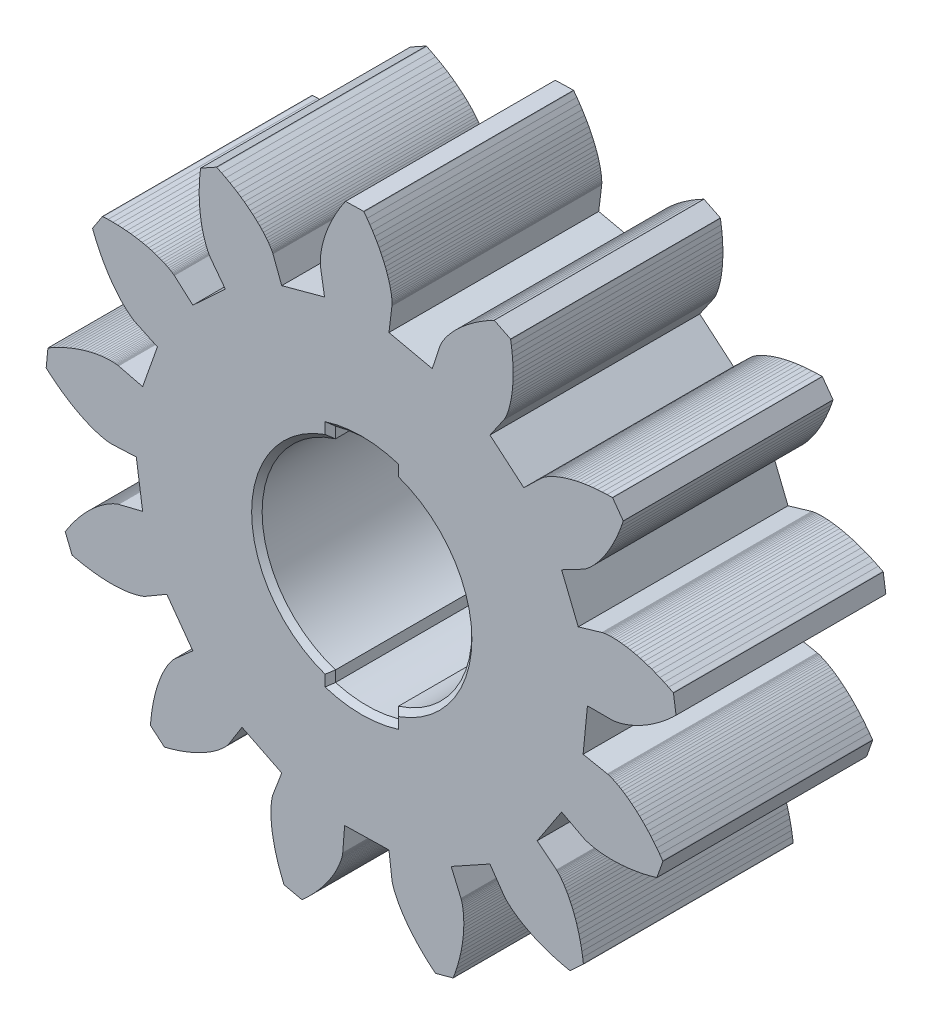
SolidWorks part; units mm, degrees
material "Stainless Steel (ferritic)"
ref_plane "Front Plane" through (0, 0, 0) normal (0, 0, 1) x (1, 0, 0)
ref_plane "Top Plane" through (0, 0, 0) normal (0, 1, 0) x (1, 0, 0)
ref_plane "Right Plane" through (0, 0, 0) normal (1, 0, 0) x (0, 0, -1)
sketch "Model" plane through (0, 0, 0) normal (0, 0, 1) x (1, 0, 0)
  line L0 (10.7591, 0) -> (11.9435, 0)
  line L1 (11.9435, 0) -> (11.9534, 0.0003)
  line L2 (11.9534, 0.0003) -> (11.9719, 0.0014)
  line L3 (11.9719, 0.0014) -> (11.9989, 0.0037)
  line L4 (11.9989, 0.0037) -> (12.0344, 0.0077)
  line L5 (12.0344, 0.0077) -> (12.0783, 0.0139)
  line L6 (12.0783, 0.0139) -> (12.1305, 0.0226)
  line L7 (12.1305, 0.0226) -> (12.191, 0.0344)
  line L8 (12.191, 0.0344) -> (12.2594, 0.0496)
  line L9 (12.2594, 0.0496) -> (12.3359, 0.0688)
  line L10 (12.3359, 0.0688) -> (12.42, 0.0923)
  line L11 (12.42, 0.0923) -> (12.5117, 0.1207)
  line L12 (12.5117, 0.1207) -> (12.6108, 0.1542)
  line L13 (12.6108, 0.1542) -> (12.717, 0.1934)
  line L14 (12.717, 0.1934) -> (12.8302, 0.2386)
  line L15 (12.8302, 0.2386) -> (12.95, 0.2902)
  line L16 (12.95, 0.2902) -> (13.0761, 0.3486)
  line L17 (13.0761, 0.3486) -> (13.2084, 0.4143)
  line L18 (13.2084, 0.4143) -> (13.3464, 0.4875)
  line L19 (13.3464, 0.4875) -> (13.49, 0.5686)
  line L20 (13.49, 0.5686) -> (13.6387, 0.6579)
  line L21 (13.6387, 0.6579) -> (13.7922, 0.7559)
  line L22 (13.7922, 0.7559) -> (13.9501, 0.8628)
  line L23 (13.9501, 0.8628) -> (14.1121, 0.9788)
  line L24 (14.1121, 0.9788) -> (14.2778, 1.1044)
  line L25 (14.2778, 1.1044) -> (14.4468, 1.2398)
  line L26 (14.4468, 1.2398) -> (14.6187, 1.3852)
  line L27 (14.6187, 1.3852) -> (14.793, 1.541)
  line L28 (14.793, 1.541) -> (14.9694, 1.7072)
  line L29 (14.9694, 1.7072) -> (14.9805, 1.718)
  line L30 (14.9805, 1.718) -> (14.9843, 1.7217)
  line L31 (14.9843, 1.7217) -> (14.8588, 2.5833)
  line L32 (14.8588, 2.5833) -> (14.8554, 2.5851)
  line L33 (14.8554, 2.5851) -> (14.8417, 2.5922)
  line L34 (14.8417, 2.5922) -> (14.6256, 2.7019)
  line L35 (14.6256, 2.7019) -> (14.4144, 2.802)
  line L36 (14.4144, 2.802) -> (14.2084, 2.8929)
  line L37 (14.2084, 2.8929) -> (14.0081, 2.975)
  line L38 (14.0081, 2.975) -> (13.8136, 3.0487)
  line L39 (13.8136, 3.0487) -> (13.6254, 3.1143)
  line L40 (13.6254, 3.1143) -> (13.4437, 3.1722)
  line L41 (13.4437, 3.1722) -> (13.2688, 3.2227)
  line L42 (13.2688, 3.2227) -> (13.1009, 3.2665)
  line L43 (13.1009, 3.2665) -> (12.9403, 3.3037)
  line L44 (12.9403, 3.3037) -> (12.7872, 3.3349)
  line L45 (12.7872, 3.3349) -> (12.6417, 3.3605)
  line L46 (12.6417, 3.3605) -> (12.5042, 3.3809)
  line L47 (12.5042, 3.3809) -> (12.3747, 3.3966)
  line L48 (12.3747, 3.3966) -> (12.2534, 3.408)
  line L49 (12.2534, 3.408) -> (12.1405, 3.4155)
  line L50 (12.1405, 3.4155) -> (12.0359, 3.4197)
  line L51 (12.0359, 3.4197) -> (11.9399, 3.4209)
  line L52 (11.9399, 3.4209) -> (11.8526, 3.4198)
  line L53 (11.8526, 3.4198) -> (11.7739, 3.4166)
  line L54 (11.7739, 3.4166) -> (11.7038, 3.4118)
  line L55 (11.7038, 3.4118) -> (11.6426, 3.406)
  line L56 (11.6426, 3.406) -> (11.59, 3.3997)
  line L57 (11.59, 3.3997) -> (11.5461, 3.3931)
  line L58 (11.5461, 3.3931) -> (11.511, 3.3869)
  line L59 (11.511, 3.3869) -> (11.4844, 3.3815)
  line L60 (11.4844, 3.3815) -> (11.4664, 3.3773)
  line L61 (11.4664, 3.3773) -> (11.4568, 3.3748)
  line L62 (11.4568, 3.3748) -> (10.3206, 3.0402)
  line L63 (10.3206, 3.0402) -> (9.5267, 5)
  line L64 (9.5267, 5) -> (10.5754, 5.5504)
  line L65 (10.5754, 5.5504) -> (10.584, 5.5553)
  line L66 (10.584, 5.5553) -> (10.5999, 5.5649)
  line L67 (10.5999, 5.5649) -> (10.6228, 5.5795)
  line L68 (10.6228, 5.5795) -> (10.6523, 5.5995)
  line L69 (10.6523, 5.5995) -> (10.6884, 5.6253)
  line L70 (10.6884, 5.6253) -> (10.7306, 5.6573)
  line L71 (10.7306, 5.6573) -> (10.7786, 5.6958)
  line L72 (10.7786, 5.6958) -> (10.8322, 5.7412)
  line L73 (10.8322, 5.7412) -> (10.8909, 5.7937)
  line L74 (10.8909, 5.7937) -> (10.9545, 5.8536)
  line L75 (10.9545, 5.8536) -> (11.0225, 5.9213)
  line L76 (11.0225, 5.9213) -> (11.0947, 5.9971)
  line L77 (11.0947, 5.9971) -> (11.1705, 6.0811)
  line L78 (11.1705, 6.0811) -> (11.2497, 6.1737)
  line L79 (11.2497, 6.1737) -> (11.3318, 6.2751)
  line L80 (11.3318, 6.2751) -> (11.4163, 6.3855)
  line L81 (11.4163, 6.3855) -> (11.5029, 6.5051)
  line L82 (11.5029, 6.5051) -> (11.5911, 6.634)
  line L83 (11.5911, 6.634) -> (11.6806, 6.7726)
  line L84 (11.6806, 6.7726) -> (11.7707, 6.9208)
  line L85 (11.7707, 6.9208) -> (11.8611, 7.0789)
  line L86 (11.8611, 7.0789) -> (11.9513, 7.2469)
  line L87 (11.9513, 7.2469) -> (12.0408, 7.425)
  line L88 (12.0408, 7.425) -> (12.1291, 7.6132)
  line L89 (12.1291, 7.6132) -> (12.2159, 7.8116)
  line L90 (12.2159, 7.8116) -> (12.3005, 8.0202)
  line L91 (12.3005, 8.0202) -> (12.3825, 8.2391)
  line L92 (12.3825, 8.2391) -> (12.4613, 8.4683)
  line L93 (12.4613, 8.4683) -> (12.4662, 8.4829)
  line L94 (12.4662, 8.4829) -> (12.4678, 8.488)
  line L95 (12.4678, 8.488) -> (11.9563, 9.1926)
  line L96 (11.9563, 9.1926) -> (11.9525, 9.1926)
  line L97 (11.9525, 9.1926) -> (11.937, 9.1926)
  line L98 (11.937, 9.1926) -> (11.6947, 9.1893)
  line L99 (11.6947, 9.1893) -> (11.4611, 9.1798)
  line L100 (11.4611, 9.1798) -> (11.2365, 9.1646)
  line L101 (11.2365, 9.1646) -> (11.0209, 9.1441)
  line L102 (11.0209, 9.1441) -> (10.8145, 9.119)
  line L103 (10.8145, 9.119) -> (10.6174, 9.0896)
  line L104 (10.6174, 9.0896) -> (10.4296, 9.0564)
  line L105 (10.4296, 9.0564) -> (10.2512, 9.0199)
  line L106 (10.2512, 9.0199) -> (10.0823, 8.9806)
  line L107 (10.0823, 8.9806) -> (9.9227, 8.9389)
  line L108 (9.9227, 8.9389) -> (9.7727, 8.8954)
  line L109 (9.7727, 8.8954) -> (9.632, 8.8505)
  line L110 (9.632, 8.8505) -> (9.5007, 8.8046)
  line L111 (9.5007, 8.8046) -> (9.3788, 8.7583)
  line L112 (9.3788, 8.7583) -> (9.2661, 8.712)
  line L113 (9.2661, 8.712) -> (9.1626, 8.6662)
  line L114 (9.1626, 8.6662) -> (9.0681, 8.6214)
  line L115 (9.0681, 8.6214) -> (8.9825, 8.5779)
  line L116 (8.9825, 8.5779) -> (8.9057, 8.5362)
  line L117 (8.9057, 8.5362) -> (8.8375, 8.4968)
  line L118 (8.8375, 8.4968) -> (8.7777, 8.4601)
  line L119 (8.7777, 8.4601) -> (8.7261, 8.4265)
  line L120 (8.7261, 8.4265) -> (8.6825, 8.3964)
  line L121 (8.6825, 8.3964) -> (8.6467, 8.3702)
  line L122 (8.6467, 8.3702) -> (8.6185, 8.3484)
  line L123 (8.6185, 8.3484) -> (8.5974, 8.3312)
  line L124 (8.5974, 8.3312) -> (8.5834, 8.3192)
  line L125 (8.5834, 8.3192) -> (8.5761, 8.3125)
  line L126 (8.5761, 8.3125) -> (7.7256, 7.4882)
  line L127 (7.7256, 7.4882) -> (6.1119, 8.8546)
  line L128 (6.1119, 8.8546) -> (6.7847, 9.8293)
  line L129 (6.7847, 9.8293) -> (6.79, 9.8376)
  line L130 (6.79, 9.8376) -> (6.7996, 9.8535)
  line L131 (6.7996, 9.8535) -> (6.8131, 9.877)
  line L132 (6.8131, 9.877) -> (6.83, 9.9085)
  line L133 (6.83, 9.9085) -> (6.8498, 9.9481)
  line L134 (6.8498, 9.9481) -> (6.8723, 9.9961)
  line L135 (6.8723, 9.9961) -> (6.897, 10.0525)
  line L136 (6.897, 10.0525) -> (6.9233, 10.1175)
  line L137 (6.9233, 10.1175) -> (6.951, 10.1913)
  line L138 (6.951, 10.1913) -> (6.9794, 10.2739)
  line L139 (6.9794, 10.2739) -> (7.0082, 10.3655)
  line L140 (7.0082, 10.3655) -> (7.0369, 10.4661)
  line L141 (7.0369, 10.4661) -> (7.065, 10.5758)
  line L142 (7.065, 10.5758) -> (7.092, 10.6945)
  line L143 (7.092, 10.6945) -> (7.1176, 10.8224)
  line L144 (7.1176, 10.8224) -> (7.1412, 10.9595)
  line L145 (7.1412, 10.9595) -> (7.1623, 11.1056)
  line L146 (7.1623, 11.1056) -> (7.1805, 11.2608)
  line L147 (7.1805, 11.2608) -> (7.1953, 11.425)
  line L148 (7.1953, 11.425) -> (7.2062, 11.5982)
  line L149 (7.2062, 11.5982) -> (7.2128, 11.7801)
  line L150 (7.2128, 11.7801) -> (7.2145, 11.9708)
  line L151 (7.2145, 11.9708) -> (7.211, 12.1701)
  line L152 (7.211, 12.1701) -> (7.2018, 12.3778)
  line L153 (7.2018, 12.3778) -> (7.1864, 12.5938)
  line L154 (7.1864, 12.5938) -> (7.1643, 12.8179)
  line L155 (7.1643, 12.8179) -> (7.1352, 13.0498)
  line L156 (7.1352, 13.0498) -> (7.0986, 13.2894)
  line L157 (7.0986, 13.2894) -> (7.096, 13.3046)
  line L158 (7.096, 13.3046) -> (7.0951, 13.3098)
  line L159 (7.0951, 13.3098) -> (6.3148, 13.696)
  line L160 (6.3148, 13.696) -> (6.3114, 13.6942)
  line L161 (6.3114, 13.6942) -> (6.2977, 13.6871)
  line L162 (6.2977, 13.6871) -> (6.0847, 13.5715)
  line L163 (6.0847, 13.5715) -> (5.8823, 13.4545)
  line L164 (5.8823, 13.4545) -> (5.6905, 13.3367)
  line L165 (5.6905, 13.3367) -> (5.5091, 13.2184)
  line L166 (5.5091, 13.2184) -> (5.338, 13.1002)
  line L167 (5.338, 13.1002) -> (5.1771, 12.9826)
  line L168 (5.1771, 12.9826) -> (5.0263, 12.8659)
  line L169 (5.0263, 12.8659) -> (4.8852, 12.7507)
  line L170 (4.8852, 12.7507) -> (4.7539, 12.6374)
  line L171 (4.7539, 12.6374) -> (4.632, 12.5264)
  line L172 (4.632, 12.5264) -> (4.5194, 12.4181)
  line L173 (4.5194, 12.4181) -> (4.4157, 12.3129)
  line L174 (4.4157, 12.3129) -> (4.3208, 12.2113)
  line L175 (4.3208, 12.2113) -> (4.2343, 12.1137)
  line L176 (4.2343, 12.1137) -> (4.156, 12.0203)
  line L177 (4.156, 12.0203) -> (4.0857, 11.9316)
  line L178 (4.0857, 11.9316) -> (4.0228, 11.848)
  line L179 (4.0228, 11.848) -> (3.9673, 11.7697)
  line L180 (3.9673, 11.7697) -> (3.9186, 11.6971)
  line L181 (3.9186, 11.6971) -> (3.8765, 11.6305)
  line L182 (3.8765, 11.6305) -> (3.8407, 11.5702)
  line L183 (3.8407, 11.5702) -> (3.8106, 11.5165)
  line L184 (3.8106, 11.5165) -> (3.786, 11.4696)
  line L185 (3.786, 11.4696) -> (3.7665, 11.4298)
  line L186 (3.7665, 11.4298) -> (3.7516, 11.3973)
  line L187 (3.7516, 11.3973) -> (3.7409, 11.3724)
  line L188 (3.7409, 11.3724) -> (3.7341, 11.3552)
  line L189 (3.7341, 11.3552) -> (3.7307, 11.3459)
  line L190 (3.7307, 11.3459) -> (3.3608, 10.2207)
  line L191 (3.3608, 10.2207) -> (1.2969, 10.6806)
  line L192 (1.2969, 10.6806) -> (1.4396, 11.8564)
  line L193 (1.4396, 11.8564) -> (1.4405, 11.8663)
  line L194 (1.4405, 11.8663) -> (1.4416, 11.8848)
  line L195 (1.4416, 11.8848) -> (1.4426, 11.9118)
  line L196 (1.4426, 11.9118) -> (1.4429, 11.9476)
  line L197 (1.4429, 11.9476) -> (1.4421, 11.9919)
  line L198 (1.4421, 11.9919) -> (1.4397, 12.0448)
  line L199 (1.4397, 12.0448) -> (1.4354, 12.1062)
  line L200 (1.4354, 12.1062) -> (1.4285, 12.176)
  line L201 (1.4285, 12.176) -> (1.4186, 12.2542)
  line L202 (1.4186, 12.2542) -> (1.4054, 12.3406)
  line L203 (1.4054, 12.3406) -> (1.3883, 12.4351)
  line L204 (1.3883, 12.4351) -> (1.367, 12.5375)
  line L205 (1.367, 12.5375) -> (1.3409, 12.6476)
  line L206 (1.3409, 12.6476) -> (1.3097, 12.7654)
  line L207 (1.3097, 12.7654) -> (1.2729, 12.8905)
  line L208 (1.2729, 12.8905) -> (1.2301, 13.0228)
  line L209 (1.2301, 13.0228) -> (1.1808, 13.162)
  line L210 (1.1808, 13.162) -> (1.1248, 13.3079)
  line L211 (1.1248, 13.3079) -> (1.0616, 13.4602)
  line L212 (1.0616, 13.4602) -> (0.9908, 13.6185)
  line L213 (0.9908, 13.6185) -> (0.9121, 13.7827)
  line L214 (0.9121, 13.7827) -> (0.825, 13.9524)
  line L215 (0.825, 13.9524) -> (0.7293, 14.1272)
  line L216 (0.7293, 14.1272) -> (0.6246, 14.3069)
  line L217 (0.6246, 14.3069) -> (0.5106, 14.4909)
  line L218 (0.5106, 14.4909) -> (0.387, 14.6791)
  line L219 (0.387, 14.6791) -> (0.2534, 14.8709)
  line L220 (0.2534, 14.8709) -> (0.1096, 15.066)
  line L221 (0.1096, 15.066) -> (0.1003, 15.0783)
  line L222 (0.1003, 15.0783) -> (0.097, 15.0825)
  line L223 (0.097, 15.0825) -> (-0.7734, 15.0619)
  line L224 (-0.7734, 15.0619) -> (-0.7756, 15.0587)
  line L225 (-0.7756, 15.0587) -> (-0.7844, 15.046)
  line L226 (-0.7844, 15.046) -> (-0.9193, 14.8446)
  line L227 (-0.9193, 14.8446) -> (-1.0441, 14.647)
  line L228 (-1.0441, 14.647) -> (-1.1592, 14.4535)
  line L229 (-1.1592, 14.4535) -> (-1.2649, 14.2645)
  line L230 (-1.2649, 14.2645) -> (-1.3614, 14.0804)
  line L231 (-1.3614, 14.0804) -> (-1.4492, 13.9014)
  line L232 (-1.4492, 13.9014) -> (-1.5286, 13.728)
  line L233 (-1.5286, 13.728) -> (-1.5999, 13.5605)
  line L234 (-1.5999, 13.5605) -> (-1.6635, 13.3991)
  line L235 (-1.6635, 13.3991) -> (-1.7198, 13.2441)
  line L236 (-1.7198, 13.2441) -> (-1.7693, 13.0959)
  line L237 (-1.7693, 13.0959) -> (-1.8122, 12.9546)
  line L238 (-1.8122, 12.9546) -> (-1.849, 12.8206)
  line L239 (-1.849, 12.8206) -> (-1.8802, 12.6939)
  line L240 (-1.8802, 12.6939) -> (-1.9061, 12.5749)
  line L241 (-1.9061, 12.5749) -> (-1.9272, 12.4636)
  line L242 (-1.9272, 12.4636) -> (-1.944, 12.3604)
  line L243 (-1.944, 12.3604) -> (-1.9568, 12.2652)
  line L244 (-1.9568, 12.2652) -> (-1.9661, 12.1784)
  line L245 (-1.9661, 12.1784) -> (-1.9725, 12.0998)
  line L246 (-1.9725, 12.0998) -> (-1.9762, 12.0298)
  line L247 (-1.9762, 12.0298) -> (-1.9779, 11.9682)
  line L248 (-1.9779, 11.9682) -> (-1.9779, 11.9153)
  line L249 (-1.9779, 11.9153) -> (-1.9767, 11.871)
  line L250 (-1.9767, 11.871) -> (-1.9747, 11.8353)
  line L251 (-1.9747, 11.8353) -> (-1.9726, 11.8082)
  line L252 (-1.9726, 11.8082) -> (-1.9706, 11.7898)
  line L253 (-1.9706, 11.7898) -> (-1.9693, 11.78)
  line L254 (-1.9693, 11.78) -> (-1.774, 10.6118)
  line L255 (-1.774, 10.6118) -> (-3.8152, 10.0599)
  line L256 (-3.8152, 10.0599) -> (-4.2352, 11.1674)
  line L257 (-4.2352, 11.1674) -> (-4.2391, 11.1765)
  line L258 (-4.2391, 11.1765) -> (-4.2466, 11.1934)
  line L259 (-4.2466, 11.1934) -> (-4.2584, 11.2178)
  line L260 (-4.2584, 11.2178) -> (-4.2747, 11.2496)
  line L261 (-4.2747, 11.2496) -> (-4.296, 11.2885)
  line L262 (-4.296, 11.2885) -> (-4.3227, 11.3342)
  line L263 (-4.3227, 11.3342) -> (-4.3551, 11.3866)
  line L264 (-4.3551, 11.3866) -> (-4.3936, 11.4452)
  line L265 (-4.3936, 11.4452) -> (-4.4387, 11.5098)
  line L266 (-4.4387, 11.5098) -> (-4.4905, 11.5802)
  line L267 (-4.4905, 11.5802) -> (-4.5495, 11.6559)
  line L268 (-4.5495, 11.6559) -> (-4.616, 11.7366)
  line L269 (-4.616, 11.7366) -> (-4.6903, 11.8221)
  line L270 (-4.6903, 11.8221) -> (-4.7727, 11.9118)
  line L271 (-4.7727, 11.9118) -> (-4.8635, 12.0055)
  line L272 (-4.8635, 12.0055) -> (-4.9628, 12.1027)
  line L273 (-4.9628, 12.1027) -> (-5.0711, 12.2031)
  line L274 (-5.0711, 12.2031) -> (-5.1885, 12.3063)
  line L275 (-5.1885, 12.3063) -> (-5.3152, 12.4117)
  line L276 (-5.3152, 12.4117) -> (-5.4515, 12.5191)
  line L277 (-5.4515, 12.5191) -> (-5.5976, 12.6279)
  line L278 (-5.5976, 12.6279) -> (-5.7535, 12.7377)
  line L279 (-5.7535, 12.7377) -> (-5.9195, 12.848)
  line L280 (-5.9195, 12.848) -> (-6.0957, 12.9584)
  line L281 (-6.0957, 12.9584) -> (-6.2822, 13.0684)
  line L282 (-6.2822, 13.0684) -> (-6.4791, 13.1775)
  line L283 (-6.4791, 13.1775) -> (-6.6865, 13.2853)
  line L284 (-6.6865, 13.2853) -> (-6.9045, 13.3912)
  line L285 (-6.9045, 13.3912) -> (-6.9185, 13.3978)
  line L286 (-6.9185, 13.3978) -> (-6.9233, 13.4)
  line L287 (-6.9233, 13.4) -> (-7.6844, 12.9772)
  line L288 (-7.6844, 12.9772) -> (-7.6849, 12.9734)
  line L289 (-7.6849, 12.9734) -> (-7.6867, 12.958)
  line L290 (-7.6867, 12.958) -> (-7.7126, 12.7171)
  line L291 (-7.7126, 12.7171) -> (-7.7313, 12.4841)
  line L292 (-7.7313, 12.4841) -> (-7.7433, 12.2592)
  line L293 (-7.7433, 12.2592) -> (-7.749, 12.0428)
  line L294 (-7.749, 12.0428) -> (-7.749, 11.8349)
  line L295 (-7.749, 11.8349) -> (-7.7435, 11.6356)
  line L296 (-7.7435, 11.6356) -> (-7.7332, 11.4452)
  line L297 (-7.7332, 11.4452) -> (-7.7185, 11.2637)
  line L298 (-7.7185, 11.2637) -> (-7.6998, 11.0912)
  line L299 (-7.6998, 11.0912) -> (-7.6777, 10.9279)
  line L300 (-7.6777, 10.9279) -> (-7.6526, 10.7736)
  line L301 (-7.6526, 10.7736) -> (-7.6249, 10.6286)
  line L302 (-7.6249, 10.6286) -> (-7.5952, 10.4927)
  line L303 (-7.5952, 10.4927) -> (-7.564, 10.3661)
  line L304 (-7.564, 10.3661) -> (-7.5316, 10.2487)
  line L305 (-7.5316, 10.2487) -> (-7.4986, 10.1404)
  line L306 (-7.4986, 10.1404) -> (-7.4655, 10.0412)
  line L307 (-7.4655, 10.0412) -> (-7.4326, 9.951)
  line L308 (-7.4326, 9.951) -> (-7.4005, 9.8697)
  line L309 (-7.4005, 9.8697) -> (-7.3696, 9.7972)
  line L310 (-7.3696, 9.7972) -> (-7.3404, 9.7334)
  line L311 (-7.3404, 9.7334) -> (-7.3132, 9.6782)
  line L312 (-7.3132, 9.6782) -> (-7.2886, 9.6313)
  line L313 (-7.2886, 9.6313) -> (-7.267, 9.5926)
  line L314 (-7.267, 9.5926) -> (-7.2487, 9.5619)
  line L315 (-7.2487, 9.5619) -> (-7.2342, 9.539)
  line L316 (-7.2342, 9.539) -> (-7.2239, 9.5236)
  line L317 (-7.2239, 9.5236) -> (-7.2182, 9.5155)
  line L318 (-7.2182, 9.5155) -> (-6.5024, 8.5719)
  line L319 (-6.5024, 8.5719) -> (-8.0533, 7.1346)
  line L320 (-8.0533, 7.1346) -> (-8.9398, 7.92)
  line L321 (-8.9398, 7.92) -> (-8.9475, 7.9263)
  line L322 (-8.9475, 7.9263) -> (-8.962, 7.9377)
  line L323 (-8.962, 7.9377) -> (-8.9838, 7.9539)
  line L324 (-8.9838, 7.9539) -> (-9.013, 7.9745)
  line L325 (-9.013, 7.9745) -> (-9.0499, 7.999)
  line L326 (-9.0499, 7.999) -> (-9.0948, 8.0271)
  line L327 (-9.0948, 8.0271) -> (-9.1478, 8.0584)
  line L328 (-9.1478, 8.0584) -> (-9.2092, 8.0924)
  line L329 (-9.2092, 8.0924) -> (-9.2791, 8.1287)
  line L330 (-9.2791, 8.1287) -> (-9.3577, 8.1669)
  line L331 (-9.3577, 8.1669) -> (-9.4452, 8.2065)
  line L332 (-9.4452, 8.2065) -> (-9.5416, 8.2471)
  line L333 (-9.5416, 8.2471) -> (-9.6471, 8.2882)
  line L334 (-9.6471, 8.2882) -> (-9.7617, 8.3294)
  line L335 (-9.7617, 8.3294) -> (-9.8856, 8.3702)
  line L336 (-9.8856, 8.3702) -> (-10.0188, 8.4101)
  line L337 (-10.0188, 8.4101) -> (-10.1613, 8.4487)
  line L338 (-10.1613, 8.4487) -> (-10.3132, 8.4855)
  line L339 (-10.3132, 8.4855) -> (-10.4744, 8.5199)
  line L340 (-10.4744, 8.5199) -> (-10.645, 8.5516)
  line L341 (-10.645, 8.5516) -> (-10.8248, 8.5801)
  line L342 (-10.8248, 8.5801) -> (-11.0139, 8.6049)
  line L343 (-11.0139, 8.6049) -> (-11.2122, 8.6254)
  line L344 (-11.2122, 8.6254) -> (-11.4195, 8.6413)
  line L345 (-11.4195, 8.6413) -> (-11.6358, 8.652)
  line L346 (-11.6358, 8.652) -> (-11.8608, 8.6571)
  line L347 (-11.8608, 8.6571) -> (-12.0946, 8.6562)
  line L348 (-12.0946, 8.6562) -> (-12.3368, 8.6487)
  line L349 (-12.3368, 8.6487) -> (-12.3522, 8.648)
  line L350 (-12.3522, 8.648) -> (-12.3575, 8.6477)
  line L351 (-12.3575, 8.6477) -> (-12.835, 7.9196)
  line L352 (-12.835, 7.9196) -> (-12.8336, 7.916)
  line L353 (-12.8336, 7.916) -> (-12.8282, 7.9016)
  line L354 (-12.8282, 7.9016) -> (-12.7391, 7.6762)
  line L355 (-12.7391, 7.6762) -> (-12.6474, 7.4612)
  line L356 (-12.6474, 7.4612) -> (-12.5535, 7.2565)
  line L357 (-12.5535, 7.2565) -> (-12.458, 7.0622)
  line L358 (-12.458, 7.0622) -> (-12.3613, 6.8781)
  line L359 (-12.3613, 6.8781) -> (-12.2639, 6.7042)
  line L360 (-12.2639, 6.7042) -> (-12.1663, 6.5404)
  line L361 (-12.1663, 6.5404) -> (-12.0689, 6.3866)
  line L362 (-12.0689, 6.3866) -> (-11.9722, 6.2425)
  line L363 (-11.9722, 6.2425) -> (-11.8767, 6.1081)
  line L364 (-11.8767, 6.1081) -> (-11.7828, 5.9833)
  line L365 (-11.7828, 5.9833) -> (-11.6909, 5.8677)
  line L366 (-11.6909, 5.8677) -> (-11.6015, 5.7612)
  line L367 (-11.6015, 5.7612) -> (-11.5149, 5.6636)
  line L368 (-11.5149, 5.6636) -> (-11.4317, 5.5746)
  line L369 (-11.4317, 5.5746) -> (-11.3522, 5.4941)
  line L370 (-11.3522, 5.4941) -> (-11.2767, 5.4216)
  line L371 (-11.2767, 5.4216) -> (-11.2057, 5.357)
  line L372 (-11.2057, 5.357) -> (-11.1395, 5.3)
  line L373 (-11.1395, 5.3) -> (-11.0785, 5.2502)
  line L374 (-11.0785, 5.2502) -> (-11.0229, 5.2073)
  line L375 (-11.0229, 5.2073) -> (-10.9732, 5.171)
  line L376 (-10.9732, 5.171) -> (-10.9296, 5.1409)
  line L377 (-10.9296, 5.1409) -> (-10.8925, 5.1167)
  line L378 (-10.8925, 5.1167) -> (-10.862, 5.098)
  line L379 (-10.862, 5.098) -> (-10.8385, 5.0845)
  line L380 (-10.8385, 5.0845) -> (-10.8223, 5.0756)
  line L381 (-10.8223, 5.0756) -> (-10.8134, 5.0711)
  line L382 (-10.8134, 5.0711) -> (-9.7411, 4.5682)
  line L383 (-9.7411, 4.5682) -> (-10.4465, 2.5748)
  line L384 (-10.4465, 2.5748) -> (-11.5964, 2.8582)
  line L385 (-11.5964, 2.8582) -> (-11.6061, 2.8603)
  line L386 (-11.6061, 2.8603) -> (-11.6243, 2.8637)
  line L387 (-11.6243, 2.8637) -> (-11.6511, 2.8679)
  line L388 (-11.6511, 2.8679) -> (-11.6866, 2.8725)
  line L389 (-11.6866, 2.8725) -> (-11.7307, 2.8771)
  line L390 (-11.7307, 2.8771) -> (-11.7834, 2.8811)
  line L391 (-11.7834, 2.8811) -> (-11.8449, 2.8841)
  line L392 (-11.8449, 2.8841) -> (-11.9151, 2.8857)
  line L393 (-11.9151, 2.8857) -> (-11.9939, 2.8854)
  line L394 (-11.9939, 2.8854) -> (-12.0812, 2.8827)
  line L395 (-12.0812, 2.8827) -> (-12.177, 2.8771)
  line L396 (-12.177, 2.8771) -> (-12.2813, 2.8682)
  line L397 (-12.2813, 2.8682) -> (-12.3938, 2.8556)
  line L398 (-12.3938, 2.8556) -> (-12.5144, 2.8388)
  line L399 (-12.5144, 2.8388) -> (-12.6431, 2.8174)
  line L400 (-12.6431, 2.8174) -> (-12.7796, 2.7908)
  line L401 (-12.7796, 2.7908) -> (-12.9237, 2.7587)
  line L402 (-12.9237, 2.7587) -> (-13.0753, 2.7207)
  line L403 (-13.0753, 2.7207) -> (-13.2341, 2.6763)
  line L404 (-13.2341, 2.6763) -> (-13.3998, 2.6251)
  line L405 (-13.3998, 2.6251) -> (-13.5723, 2.5668)
  line L406 (-13.5723, 2.5668) -> (-13.7512, 2.5008)
  line L407 (-13.7512, 2.5008) -> (-13.9363, 2.4269)
  line L408 (-13.9363, 2.4269) -> (-14.1273, 2.3446)
  line L409 (-14.1273, 2.3446) -> (-14.3237, 2.2536)
  line L410 (-14.3237, 2.2536) -> (-14.5254, 2.1535)
  line L411 (-14.5254, 2.1535) -> (-14.7319, 2.044)
  line L412 (-14.7319, 2.044) -> (-14.943, 1.9248)
  line L413 (-14.943, 1.9248) -> (-14.9563, 1.917)
  line L414 (-14.9563, 1.917) -> (-14.9609, 1.9143)
  line L415 (-14.9609, 1.9143) -> (-15.0453, 1.0477)
  line L416 (-15.0453, 1.0477) -> (-15.0424, 1.0452)
  line L417 (-15.0424, 1.0452) -> (-15.0308, 1.0349)
  line L418 (-15.0308, 1.0349) -> (-14.8472, 0.8768)
  line L419 (-14.8472, 0.8768) -> (-14.6661, 0.729)
  line L420 (-14.6661, 0.729) -> (-14.4879, 0.5914)
  line L421 (-14.4879, 0.5914) -> (-14.313, 0.4637)
  line L422 (-14.313, 0.4637) -> (-14.1418, 0.3457)
  line L423 (-14.1418, 0.3457) -> (-13.9748, 0.237)
  line L424 (-13.9748, 0.237) -> (-13.8122, 0.1373)
  line L425 (-13.8122, 0.1373) -> (-13.6545, 0.0463)
  line L426 (-13.6545, 0.0463) -> (-13.5019, -0.0363)
  line L427 (-13.5019, -0.0363) -> (-13.3549, -0.1109)
  line L428 (-13.3549, -0.1109) -> (-13.2137, -0.1778)
  line L429 (-13.2137, -0.1778) -> (-13.0786, -0.2375)
  line L430 (-13.0786, -0.2375) -> (-12.95, -0.2902)
  line L431 (-12.95, -0.2902) -> (-12.828, -0.3364)
  line L432 (-12.828, -0.3364) -> (-12.7129, -0.3765)
  line L433 (-12.7129, -0.3765) -> (-12.6051, -0.4109)
  line L434 (-12.6051, -0.4109) -> (-12.5046, -0.4399)
  line L435 (-12.5046, -0.4399) -> (-12.4117, -0.4641)
  line L436 (-12.4117, -0.4641) -> (-12.3265, -0.4839)
  line L437 (-12.3265, -0.4839) -> (-12.2494, -0.4996)
  line L438 (-12.2494, -0.4996) -> (-12.1803, -0.5118)
  line L439 (-12.1803, -0.5118) -> (-12.1194, -0.5208)
  line L440 (-12.1194, -0.5208) -> (-12.0668, -0.5272)
  line L441 (-12.0668, -0.5272) -> (-12.0227, -0.5314)
  line L442 (-12.0227, -0.5314) -> (-11.987, -0.5338)
  line L443 (-11.987, -0.5338) -> (-11.9599, -0.5349)
  line L444 (-11.9599, -0.5349) -> (-11.9414, -0.5351)
  line L445 (-11.9414, -0.5351) -> (-11.9315, -0.535)
  line L446 (-11.9315, -0.535) -> (-10.7483, -0.482)
  line L447 (-10.7483, -0.482) -> (-10.4465, -2.5748)
  line L448 (-10.4465, -2.5748) -> (-11.5964, -2.8583)
  line L449 (-11.5964, -2.8583) -> (-11.606, -2.861)
  line L450 (-11.606, -2.861) -> (-11.6236, -2.8664)
  line L451 (-11.6236, -2.8664) -> (-11.6493, -2.8752)
  line L452 (-11.6493, -2.8752) -> (-11.6828, -2.8875)
  line L453 (-11.6828, -2.8875) -> (-11.724, -2.904)
  line L454 (-11.724, -2.904) -> (-11.7726, -2.925)
  line L455 (-11.7726, -2.925) -> (-11.8285, -2.9508)
  line L456 (-11.8285, -2.9508) -> (-11.8913, -2.982)
  line L457 (-11.8913, -2.982) -> (-11.9609, -3.019)
  line L458 (-11.9609, -3.019) -> (-12.037, -3.0619)
  line L459 (-12.037, -3.0619) -> (-12.1193, -3.1114)
  line L460 (-12.1193, -3.1114) -> (-12.2075, -3.1677)
  line L461 (-12.2075, -3.1677) -> (-12.3012, -3.2311)
  line L462 (-12.3012, -3.2311) -> (-12.4003, -3.3021)
  line L463 (-12.4003, -3.3021) -> (-12.5042, -3.3809)
  line L464 (-12.5042, -3.3809) -> (-12.6127, -3.4678)
  line L465 (-12.6127, -3.4678) -> (-12.7254, -3.5632)
  line L466 (-12.7254, -3.5632) -> (-12.842, -3.6673)
  line L467 (-12.842, -3.6673) -> (-12.9619, -3.7804)
  line L468 (-12.9619, -3.7804) -> (-13.0849, -3.9028)
  line L469 (-13.0849, -3.9028) -> (-13.2105, -4.0346)
  line L470 (-13.2105, -4.0346) -> (-13.3383, -4.1762)
  line L471 (-13.3383, -4.1762) -> (-13.4678, -4.3277)
  line L472 (-13.4678, -4.3277) -> (-13.5986, -4.4893)
  line L473 (-13.5986, -4.4893) -> (-13.7303, -4.6611)
  line L474 (-13.7303, -4.6611) -> (-13.8624, -4.8435)
  line L475 (-13.8624, -4.8435) -> (-13.9944, -5.0364)
  line L476 (-13.9944, -5.0364) -> (-14.1258, -5.24)
  line L477 (-14.1258, -5.24) -> (-14.134, -5.2531)
  line L478 (-14.134, -5.2531) -> (-14.1368, -5.2576)
  line L479 (-14.1368, -5.2576) -> (-13.8088, -6.0642)
  line L480 (-13.8088, -6.0642) -> (-13.8051, -6.0651)
  line L481 (-13.8051, -6.0651) -> (-13.7901, -6.0688)
  line L482 (-13.7901, -6.0688) -> (-13.554, -6.1235)
  line L483 (-13.554, -6.1235) -> (-13.325, -6.1702)
  line L484 (-13.325, -6.1702) -> (-13.1032, -6.2092)
  line L485 (-13.1032, -6.2092) -> (-12.889, -6.241)
  line L486 (-12.889, -6.241) -> (-12.6826, -6.2659)
  line L487 (-12.6826, -6.2659) -> (-12.4842, -6.2846)
  line L488 (-12.4842, -6.2846) -> (-12.2939, -6.2973)
  line L489 (-12.2939, -6.2973) -> (-12.1119, -6.3045)
  line L490 (-12.1119, -6.3045) -> (-11.9385, -6.3068)
  line L491 (-11.9385, -6.3068) -> (-11.7736, -6.3045)
  line L492 (-11.7736, -6.3045) -> (-11.6175, -6.2982)
  line L493 (-11.6175, -6.2982) -> (-11.4702, -6.2882)
  line L494 (-11.4702, -6.2882) -> (-11.3318, -6.2751)
  line L495 (-11.3318, -6.2751) -> (-11.2023, -6.2593)
  line L496 (-11.2023, -6.2593) -> (-11.0818, -6.2414)
  line L497 (-11.0818, -6.2414) -> (-10.9703, -6.2217)
  line L498 (-10.9703, -6.2217) -> (-10.8678, -6.2007)
  line L499 (-10.8678, -6.2007) -> (-10.7743, -6.179)
  line L500 (-10.7743, -6.179) -> (-10.6897, -6.1569)
  line L501 (-10.6897, -6.1569) -> (-10.6141, -6.1349)
  line L502 (-10.6141, -6.1349) -> (-10.5472, -6.1136)
  line L503 (-10.5472, -6.1136) -> (-10.4891, -6.0933)
  line L504 (-10.4891, -6.0933) -> (-10.4396, -6.0745)
  line L505 (-10.4396, -6.0745) -> (-10.3986, -6.0577)
  line L506 (-10.3986, -6.0577) -> (-10.3659, -6.0433)
  line L507 (-10.3659, -6.0433) -> (-10.3414, -6.0316)
  line L508 (-10.3414, -6.0316) -> (-10.3249, -6.0233)
  line L509 (-10.3249, -6.0233) -> (-10.3162, -6.0186)
  line L510 (-10.3162, -6.0186) -> (-9.2932, -5.4217)
  line L511 (-9.2932, -5.4217) -> (-8.0533, -7.1346)
  line L512 (-8.0533, -7.1346) -> (-8.9398, -7.92)
  line L513 (-8.9398, -7.92) -> (-8.947, -7.9268)
  line L514 (-8.947, -7.9268) -> (-8.9601, -7.9399)
  line L515 (-8.9601, -7.9399) -> (-8.9788, -7.9595)
  line L516 (-8.9788, -7.9595) -> (-9.0027, -7.9861)
  line L517 (-9.0027, -7.9861) -> (-9.0316, -8.0198)
  line L518 (-9.0316, -8.0198) -> (-9.0649, -8.0609)
  line L519 (-9.0649, -8.0609) -> (-9.1023, -8.1098)
  line L520 (-9.1023, -8.1098) -> (-9.1434, -8.1667)
  line L521 (-9.1434, -8.1667) -> (-9.1879, -8.2317)
  line L522 (-9.1879, -8.2317) -> (-9.2353, -8.3051)
  line L523 (-9.2353, -8.3051) -> (-9.2852, -8.3871)
  line L524 (-9.2852, -8.3871) -> (-9.3371, -8.4779)
  line L525 (-9.3371, -8.4779) -> (-9.3906, -8.5777)
  line L526 (-9.3906, -8.5777) -> (-9.4453, -8.6865)
  line L527 (-9.4453, -8.6865) -> (-9.5007, -8.8046)
  line L528 (-9.5007, -8.8046) -> (-9.5564, -8.932)
  line L529 (-9.5564, -8.932) -> (-9.6119, -9.0689)
  line L530 (-9.6119, -9.0689) -> (-9.6667, -9.2152)
  line L531 (-9.6667, -9.2152) -> (-9.7204, -9.3711)
  line L532 (-9.7204, -9.3711) -> (-9.7724, -9.5366)
  line L533 (-9.7724, -9.5366) -> (-9.8223, -9.7117)
  line L534 (-9.8223, -9.7117) -> (-9.8697, -9.8964)
  line L535 (-9.8697, -9.8964) -> (-9.914, -10.0908)
  line L536 (-9.914, -10.0908) -> (-9.9547, -10.2946)
  line L537 (-9.9547, -10.2946) -> (-9.9915, -10.508)
  line L538 (-9.9915, -10.508) -> (-10.0237, -10.7309)
  line L539 (-10.0237, -10.7309) -> (-10.0509, -10.963)
  line L540 (-10.0509, -10.963) -> (-10.0726, -11.2044)
  line L541 (-10.0726, -11.2044) -> (-10.0738, -11.2198)
  line L542 (-10.0738, -11.2198) -> (-10.0742, -11.2251)
  line L543 (-10.0742, -11.2251) -> (-9.409, -11.7868)
  line L544 (-9.409, -11.7868) -> (-9.4052, -11.7859)
  line L545 (-9.4052, -11.7859) -> (-9.3902, -11.7822)
  line L546 (-9.3902, -11.7822) -> (-9.1557, -11.721)
  line L547 (-9.1557, -11.721) -> (-8.9312, -11.6558)
  line L548 (-8.9312, -11.6558) -> (-8.7168, -11.5873)
  line L549 (-8.7168, -11.5873) -> (-8.5124, -11.5159)
  line L550 (-8.5124, -11.5159) -> (-8.318, -11.4421)
  line L551 (-8.318, -11.4421) -> (-8.1336, -11.3664)
  line L552 (-8.1336, -11.3664) -> (-7.9592, -11.2892)
  line L553 (-7.9592, -11.2892) -> (-7.7947, -11.2111)
  line L554 (-7.7947, -11.2111) -> (-7.6401, -11.1325)
  line L555 (-7.6401, -11.1325) -> (-7.4952, -11.0538)
  line L556 (-7.4952, -11.0538) -> (-7.3599, -10.9757)
  line L557 (-7.3599, -10.9757) -> (-7.2341, -10.8984)
  line L558 (-7.2341, -10.8984) -> (-7.1176, -10.8224)
  line L559 (-7.1176, -10.8224) -> (-7.0103, -10.7483)
  line L560 (-7.0103, -10.7483) -> (-6.9119, -10.6764)
  line L561 (-6.9119, -10.6764) -> (-6.8224, -10.6072)
  line L562 (-6.8224, -10.6072) -> (-6.7414, -10.541)
  line L563 (-6.7414, -10.541) -> (-6.6687, -10.4783)
  line L564 (-6.6687, -10.4783) -> (-6.6041, -10.4194)
  line L565 (-6.6041, -10.4194) -> (-6.5473, -10.3648)
  line L566 (-6.5473, -10.3648) -> (-6.498, -10.3149)
  line L567 (-6.498, -10.3149) -> (-6.456, -10.2699)
  line L568 (-6.456, -10.2699) -> (-6.4209, -10.2303)
  line L569 (-6.4209, -10.2303) -> (-6.3923, -10.1963)
  line L570 (-6.3923, -10.1963) -> (-6.3701, -10.1683)
  line L571 (-6.3701, -10.1683) -> (-6.3538, -10.1466)
  line L572 (-6.3538, -10.1466) -> (-6.3431, -10.1316)
  line L573 (-6.3431, -10.1316) -> (-6.3376, -10.1233)
  line L574 (-6.3376, -10.1233) -> (-5.7091, -9.1195)
  line L575 (-5.7091, -9.1195) -> (-3.8152, -10.0599)
  line L576 (-3.8152, -10.0599) -> (-4.2352, -11.1674)
  line L577 (-4.2352, -11.1674) -> (-4.2384, -11.1767)
  line L578 (-4.2384, -11.1767) -> (-4.2439, -11.1944)
  line L579 (-4.2439, -11.1944) -> (-4.2514, -11.2205)
  line L580 (-4.2514, -11.2205) -> (-4.2602, -11.2551)
  line L581 (-4.2602, -11.2551) -> (-4.2701, -11.2983)
  line L582 (-4.2701, -11.2983) -> (-4.2804, -11.3503)
  line L583 (-4.2804, -11.3503) -> (-4.2909, -11.4109)
  line L584 (-4.2909, -11.4109) -> (-4.3009, -11.4804)
  line L585 (-4.3009, -11.4804) -> (-4.31, -11.5586)
  line L586 (-4.31, -11.5586) -> (-4.3179, -11.6456)
  line L587 (-4.3179, -11.6456) -> (-4.3239, -11.7415)
  line L588 (-4.3239, -11.7415) -> (-4.3277, -11.846)
  line L589 (-4.3277, -11.846) -> (-4.3287, -11.9592)
  line L590 (-4.3287, -11.9592) -> (-4.3266, -12.081)
  line L591 (-4.3266, -12.081) -> (-4.3208, -12.2113)
  line L592 (-4.3208, -12.2113) -> (-4.3109, -12.35)
  line L593 (-4.3109, -12.35) -> (-4.2964, -12.497)
  line L594 (-4.2964, -12.497) -> (-4.2769, -12.652)
  line L595 (-4.2769, -12.652) -> (-4.252, -12.815)
  line L596 (-4.252, -12.815) -> (-4.2212, -12.9857)
  line L597 (-4.2212, -12.9857) -> (-4.184, -13.164)
  line L598 (-4.184, -13.164) -> (-4.1401, -13.3495)
  line L599 (-4.1401, -13.3495) -> (-4.089, -13.5422)
  line L600 (-4.089, -13.5422) -> (-4.0303, -13.7416)
  line L601 (-4.0303, -13.7416) -> (-3.9637, -13.9477)
  line L602 (-3.9637, -13.9477) -> (-3.8886, -14.1599)
  line L603 (-3.8886, -14.1599) -> (-3.8049, -14.3782)
  line L604 (-3.8049, -14.3782) -> (-3.7119, -14.602)
  line L605 (-3.7119, -14.602) -> (-3.7058, -14.6162)
  line L606 (-3.7058, -14.6162) -> (-3.7037, -14.621)
  line L607 (-3.7037, -14.621) -> (-2.8536, -14.8093)
  line L608 (-2.8536, -14.8093) -> (-2.8507, -14.8067)
  line L609 (-2.8507, -14.8067) -> (-2.8392, -14.7965)
  line L610 (-2.8392, -14.7965) -> (-2.66, -14.6333)
  line L611 (-2.66, -14.6333) -> (-2.4915, -14.4713)
  line L612 (-2.4915, -14.4713) -> (-2.3334, -14.311)
  line L613 (-2.3334, -14.311) -> (-2.1856, -14.1527)
  line L614 (-2.1856, -14.1527) -> (-2.0478, -13.997)
  line L615 (-2.0478, -13.997) -> (-1.9197, -13.8443)
  line L616 (-1.9197, -13.8443) -> (-1.8012, -13.6949)
  line L617 (-1.8012, -13.6949) -> (-1.6919, -13.5493)
  line L618 (-1.6919, -13.5493) -> (-1.5915, -13.4078)
  line L619 (-1.5915, -13.4078) -> (-1.4997, -13.2709)
  line L620 (-1.4997, -13.2709) -> (-1.4162, -13.1388)
  line L621 (-1.4162, -13.1388) -> (-1.3407, -13.0119)
  line L622 (-1.3407, -13.0119) -> (-1.2729, -12.8905)
  line L623 (-1.2729, -12.8905) -> (-1.2123, -12.775)
  line L624 (-1.2123, -12.775) -> (-1.1586, -12.6656)
  line L625 (-1.1586, -12.6656) -> (-1.1115, -12.5627)
  line L626 (-1.1115, -12.5627) -> (-1.0705, -12.4664)
  line L627 (-1.0705, -12.4664) -> (-1.0353, -12.3771)
  line L628 (-1.0353, -12.3771) -> (-1.0055, -12.295)
  line L629 (-1.0055, -12.295) -> (-0.9805, -12.2203)
  line L630 (-0.9805, -12.2203) -> (-0.9601, -12.1531)
  line L631 (-0.9601, -12.1531) -> (-0.9438, -12.0938)
  line L632 (-0.9438, -12.0938) -> (-0.9311, -12.0424)
  line L633 (-0.9311, -12.0424) -> (-0.9217, -11.999)
  line L634 (-0.9217, -11.999) -> (-0.915, -11.9639)
  line L635 (-0.915, -11.9639) -> (-0.9107, -11.9372)
  line L636 (-0.9107, -11.9372) -> (-0.9082, -11.9188)
  line L637 (-0.9082, -11.9188) -> (-0.9071, -11.909)
  line L638 (-0.9071, -11.909) -> (-0.8171, -10.728)
  line L639 (-0.8171, -10.728) -> (1.2969, -10.6806)
  line L640 (1.2969, -10.6806) -> (1.4396, -11.8564)
  line L641 (1.4396, -11.8564) -> (1.4412, -11.8662)
  line L642 (1.4412, -11.8662) -> (1.4445, -11.8844)
  line L643 (1.4445, -11.8844) -> (1.45, -11.911)
  line L644 (1.45, -11.911) -> (1.4583, -11.9457)
  line L645 (1.4583, -11.9457) -> (1.4696, -11.9886)
  line L646 (1.4696, -11.9886) -> (1.4846, -12.0394)
  line L647 (1.4846, -12.0394) -> (1.5036, -12.0979)
  line L648 (1.5036, -12.0979) -> (1.527, -12.1641)
  line L649 (1.527, -12.1641) -> (1.5552, -12.2376)
  line L650 (1.5552, -12.2376) -> (1.5887, -12.3183)
  line L651 (1.5887, -12.3183) -> (1.6279, -12.406)
  line L652 (1.6279, -12.406) -> (1.6731, -12.5003)
  line L653 (1.6731, -12.5003) -> (1.7248, -12.601)
  line L654 (1.7248, -12.601) -> (1.7833, -12.7079)
  line L655 (1.7833, -12.7079) -> (1.849, -12.8206)
  line L656 (1.849, -12.8206) -> (1.9222, -12.9387)
  line L657 (1.9222, -12.9387) -> (2.0033, -13.0621)
  line L658 (2.0033, -13.0621) -> (2.0926, -13.1904)
  line L659 (2.0926, -13.1904) -> (2.1905, -13.3231)
  line L660 (2.1905, -13.3231) -> (2.2971, -13.4599)
  line L661 (2.2971, -13.4599) -> (2.4129, -13.6005)
  line L662 (2.4129, -13.6005) -> (2.538, -13.7444)
  line L663 (2.538, -13.7444) -> (2.6727, -13.8913)
  line L664 (2.6727, -13.8913) -> (2.8174, -14.0406)
  line L665 (2.8174, -14.0406) -> (2.9721, -14.1921)
  line L666 (2.9721, -14.1921) -> (3.1372, -14.3451)
  line L667 (3.1372, -14.3451) -> (3.3128, -14.4994)
  line L668 (3.3128, -14.4994) -> (3.4991, -14.6545)
  line L669 (3.4991, -14.6545) -> (3.5111, -14.6642)
  line L670 (3.5111, -14.6642) -> (3.5153, -14.6675)
  line L671 (3.5153, -14.6675) -> (4.3555, -14.4391)
  line L672 (4.3555, -14.4391) -> (4.3568, -14.4355)
  line L673 (4.3568, -14.4355) -> (4.3623, -14.4211)
  line L674 (4.3623, -14.4211) -> (4.4451, -14.1933)
  line L675 (4.4451, -14.1933) -> (4.519, -13.9715)
  line L676 (4.519, -13.9715) -> (4.5845, -13.7561)
  line L677 (4.5845, -13.7561) -> (4.6418, -13.5473)
  line L678 (4.6418, -13.5473) -> (4.6915, -13.3454)
  line L679 (4.6915, -13.3454) -> (4.7339, -13.1507)
  line L680 (4.7339, -13.1507) -> (4.7695, -12.9633)
  line L681 (4.7695, -12.9633) -> (4.7986, -12.7836)
  line L682 (4.7986, -12.7836) -> (4.8218, -12.6116)
  line L683 (4.8218, -12.6116) -> (4.8394, -12.4477)
  line L684 (4.8394, -12.4477) -> (4.8519, -12.2919)
  line L685 (4.8519, -12.2919) -> (4.8598, -12.1445)
  line L686 (4.8598, -12.1445) -> (4.8635, -12.0055)
  line L687 (4.8635, -12.0055) -> (4.8634, -11.8751)
  line L688 (4.8634, -11.8751) -> (4.8601, -11.7533)
  line L689 (4.8601, -11.7533) -> (4.854, -11.6402)
  line L690 (4.854, -11.6402) -> (4.8455, -11.536)
  line L691 (4.8455, -11.536) -> (4.8352, -11.4405)
  line L692 (4.8352, -11.4405) -> (4.8235, -11.3539)
  line L693 (4.8235, -11.3539) -> (4.8108, -11.2762)
  line L694 (4.8108, -11.2762) -> (4.7977, -11.2073)
  line L695 (4.7977, -11.2073) -> (4.7846, -11.1471)
  line L696 (4.7846, -11.1471) -> (4.7719, -11.0957)
  line L697 (4.7719, -11.0957) -> (4.7601, -11.053)
  line L698 (4.7601, -11.053) -> (4.7497, -11.0188)
  line L699 (4.7497, -11.0188) -> (4.7411, -10.9931)
  line L700 (4.7411, -10.9931) -> (4.7348, -10.9757)
  line L701 (4.7348, -10.9757) -> (4.7312, -10.9664)
  line L702 (4.7312, -10.9664) -> (4.262, -9.8789)
  line L703 (4.262, -9.8789) -> (6.1119, -8.8546)
  line L704 (6.1119, -8.8546) -> (6.7847, -9.8293)
  line L705 (6.7847, -9.8293) -> (6.7906, -9.8372)
  line L706 (6.7906, -9.8372) -> (6.802, -9.8518)
  line L707 (6.802, -9.8518) -> (6.8192, -9.8728)
  line L708 (6.8192, -9.8728) -> (6.8427, -9.8997)
  line L709 (6.8427, -9.8997) -> (6.8727, -9.9324)
  line L710 (6.8727, -9.9324) -> (6.9095, -9.9704)
  line L711 (6.9095, -9.9704) -> (6.9535, -10.0134)
  line L712 (6.9535, -10.0134) -> (7.005, -10.0611)
  line L713 (7.005, -10.0611) -> (7.0642, -10.1131)
  line L714 (7.0642, -10.1131) -> (7.1314, -10.169)
  line L715 (7.1314, -10.169) -> (7.2068, -10.2284)
  line L716 (7.2068, -10.2284) -> (7.2907, -10.2909)
  line L717 (7.2907, -10.2909) -> (7.3832, -10.3561)
  line L718 (7.3832, -10.3561) -> (7.4847, -10.4235)
  line L719 (7.4847, -10.4235) -> (7.5952, -10.4927)
  line L720 (7.5952, -10.4927) -> (7.715, -10.5634)
  line L721 (7.715, -10.5634) -> (7.8442, -10.6349)
  line L722 (7.8442, -10.6349) -> (7.9828, -10.707)
  line L723 (7.9828, -10.707) -> (8.1311, -10.7791)
  line L724 (8.1311, -10.7791) -> (8.2891, -10.8507)
  line L725 (8.2891, -10.8507) -> (8.4569, -10.9213)
  line L726 (8.4569, -10.9213) -> (8.6346, -10.9906)
  line L727 (8.6346, -10.9906) -> (8.8222, -11.058)
  line L728 (8.8222, -11.058) -> (9.0197, -11.123)
  line L729 (9.0197, -11.123) -> (9.2271, -11.1852)
  line L730 (9.2271, -11.1852) -> (9.4444, -11.2441)
  line L731 (9.4444, -11.2441) -> (9.6716, -11.2991)
  line L732 (9.6716, -11.2991) -> (9.9086, -11.3498)
  line L733 (9.9086, -11.3498) -> (9.9237, -11.3528)
  line L734 (9.9237, -11.3528) -> (9.9289, -11.3538)
  line L735 (9.9289, -11.3538) -> (10.5668, -10.7611)
  line L736 (10.5668, -10.7611) -> (10.5663, -10.7573)
  line L737 (10.5663, -10.7573) -> (10.5644, -10.7419)
  line L738 (10.5644, -10.7419) -> (10.5319, -10.5018)
  line L739 (10.5319, -10.5018) -> (10.4943, -10.2711)
  line L740 (10.4943, -10.2711) -> (10.4522, -10.0499)
  line L741 (10.4522, -10.0499) -> (10.4059, -9.8384)
  line L742 (10.4059, -9.8384) -> (10.3561, -9.6365)
  line L743 (10.3561, -9.6365) -> (10.3031, -9.4444)
  line L744 (10.3031, -9.4444) -> (10.2475, -9.262)
  line L745 (10.2475, -9.262) -> (10.1898, -9.0893)
  line L746 (10.1898, -9.0893) -> (10.1304, -8.9263)
  line L747 (10.1304, -8.9263) -> (10.0698, -8.7729)
  line L748 (10.0698, -8.7729) -> (10.0085, -8.6292)
  line L749 (10.0085, -8.6292) -> (9.9469, -8.495)
  line L750 (9.9469, -8.495) -> (9.8856, -8.3702)
  line L751 (9.8856, -8.3702) -> (9.825, -8.2547)
  line L752 (9.825, -8.2547) -> (9.7654, -8.1484)
  line L753 (9.7654, -8.1484) -> (9.7075, -8.0512)
  line L754 (9.7075, -8.0512) -> (9.6515, -7.9628)
  line L755 (9.6515, -7.9628) -> (9.5981, -7.8831)
  line L756 (9.5981, -7.8831) -> (9.5474, -7.8118)
  line L757 (9.5474, -7.8118) -> (9.5001, -7.7489)
  line L758 (9.5001, -7.7489) -> (9.4564, -7.6939)
  line L759 (9.4564, -7.6939) -> (9.4168, -7.6468)
  line L760 (9.4168, -7.6468) -> (9.3817, -7.6072)
  line L761 (9.3817, -7.6072) -> (9.3514, -7.5748)
  line L762 (9.3514, -7.5748) -> (9.3264, -7.5493)
  line L763 (9.3264, -7.5493) -> (9.3068, -7.5305)
  line L764 (9.3068, -7.5305) -> (9.2931, -7.5181)
  line L765 (9.2931, -7.5181) -> (9.2856, -7.5116)
  line L766 (9.2856, -7.5116) -> (8.3648, -6.7667)
  line L767 (8.3648, -6.7667) -> (9.5267, -5)
  line L768 (9.5267, -5) -> (10.5755, -5.5504)
  line L769 (10.5755, -5.5504) -> (10.5844, -5.5547)
  line L770 (10.5844, -5.5547) -> (10.6012, -5.5623)
  line L771 (10.6012, -5.5623) -> (10.6262, -5.5728)
  line L772 (10.6262, -5.5728) -> (10.6595, -5.5858)
  line L773 (10.6595, -5.5858) -> (10.7013, -5.6008)
  line L774 (10.7013, -5.6008) -> (10.7515, -5.6173)
  line L775 (10.7515, -5.6173) -> (10.8105, -5.635)
  line L776 (10.8105, -5.635) -> (10.8783, -5.6533)
  line L777 (10.8783, -5.6533) -> (10.9548, -5.6718)
  line L778 (10.9548, -5.6718) -> (11.0403, -5.6901)
  line L779 (11.0403, -5.6901) -> (11.1347, -5.7077)
  line L780 (11.1347, -5.7077) -> (11.238, -5.724)
  line L781 (11.238, -5.724) -> (11.3502, -5.7387)
  line L782 (11.3502, -5.7387) -> (11.4714, -5.7512)
  line L783 (11.4714, -5.7512) -> (11.6015, -5.7612)
  line L784 (11.6015, -5.7612) -> (11.7403, -5.7681)
  line L785 (11.7403, -5.7681) -> (11.888, -5.7714)
  line L786 (11.888, -5.7714) -> (12.0442, -5.7708)
  line L787 (12.0442, -5.7708) -> (12.209, -5.7657)
  line L788 (12.209, -5.7657) -> (12.3822, -5.7556)
  line L789 (12.3822, -5.7556) -> (12.5636, -5.7402)
  line L790 (12.5636, -5.7402) -> (12.7532, -5.719)
  line L791 (12.7532, -5.719) -> (12.9506, -5.6915)
  line L792 (12.9506, -5.6915) -> (13.1557, -5.6573)
  line L793 (13.1557, -5.6573) -> (13.3682, -5.616)
  line L794 (13.3682, -5.616) -> (13.588, -5.5671)
  line L795 (13.588, -5.5671) -> (13.8147, -5.5102)
  line L796 (13.8147, -5.5102) -> (14.0481, -5.445)
  line L797 (14.0481, -5.445) -> (14.0629, -5.4406)
  line L798 (14.0629, -5.4406) -> (14.068, -5.4391)
  line L799 (14.068, -5.4391) -> (14.3573, -4.6179)
  line L800 (14.3573, -4.6179) -> (14.3551, -4.6147)
  line L801 (14.3551, -4.6147) -> (14.3464, -4.602)
  line L802 (14.3464, -4.602) -> (14.206, -4.4044)
  line L803 (14.206, -4.4044) -> (14.0655, -4.2176)
  line L804 (14.0655, -4.2176) -> (13.9253, -4.0414)
  line L805 (13.9253, -4.0414) -> (13.7861, -3.8756)
  line L806 (13.7861, -3.8756) -> (13.6482, -3.72)
  line L807 (13.6482, -3.72) -> (13.512, -3.5745)
  line L808 (13.512, -3.5745) -> (13.378, -3.4388)
  line L809 (13.378, -3.4388) -> (13.2466, -3.3127)
  line L810 (13.2466, -3.3127) -> (13.1183, -3.196)
  line L811 (13.1183, -3.196) -> (12.9933, -3.0884)
  line L812 (12.9933, -3.0884) -> (12.8723, -2.9896)
  line L813 (12.8723, -2.9896) -> (12.7554, -2.8994)
  line L814 (12.7554, -2.8994) -> (12.6431, -2.8174)
  line L815 (12.6431, -2.8174) -> (12.5357, -2.7433)
  line L816 (12.5357, -2.7433) -> (12.4336, -2.6769)
  line L817 (12.4336, -2.6769) -> (12.3371, -2.6177)
  line L818 (12.3371, -2.6177) -> (12.2465, -2.5654)
  line L819 (12.2465, -2.5654) -> (12.1621, -2.5197)
  line L820 (12.1621, -2.5197) -> (12.0842, -2.4801)
  line L821 (12.0842, -2.4801) -> (12.013, -2.4464)
  line L822 (12.013, -2.4464) -> (11.9488, -2.418)
  line L823 (11.9488, -2.418) -> (11.8918, -2.3947)
  line L824 (11.8918, -2.3947) -> (11.8423, -2.3759)
  line L825 (11.8423, -2.3759) -> (11.8005, -2.3613)
  line L826 (11.8005, -2.3613) -> (11.7664, -2.3504)
  line L827 (11.7664, -2.3504) -> (11.7404, -2.3429)
  line L828 (11.7404, -2.3429) -> (11.7225, -2.3382)
  line L829 (11.7225, -2.3382) -> (11.7128, -2.3359)
  line L830 (11.7128, -2.3359) -> (10.5513, -2.1043)
  line L831 (10.5513, -2.1043) -> (10.7591, 0)
  line L832 (-1.5, 5.5) -> (0, 5.5) construction
  line L833 (0, -5.5) -> (1.5, -5.5) construction
  line L834 (-1.5, -5.2915) -> (-1.5, 5.2915)
  line L835 (0, 5.5) -> (1.5, 5.5) construction
  line L836 (1.5, -5.2915) -> (1.5, 5.2915)
  line L837 (-1.4471, -5.3062) -> (1.4471, 5.3062) construction
  line L838 (-1.4471, 5.3062) -> (1.4471, -5.3062) construction
  line L839 (-1.5, 5.5) -> (-1.4471, 5.3062) construction
  line L840 (-1.5, 5.2915) -> (-1.5, 5.5) construction
  line L841 (1.4471, 5.3062) -> (1.5, 5.5) construction
  line L842 (1.5, 5.2915) -> (1.5, 5.5) construction
  line L843 (-1.5, -5.5) -> (-1.5, -5.2915) construction
  line L844 (-1.5, -5.5) -> (-1.4471, -5.3062) construction
  line L845 (-1.5, -5.5) -> (0, -5.5) construction
  line L846 (1.4471, -5.3062) -> (1.5, -5.5) construction
  line L847 (1.5, -5.5) -> (1.5, -5.2915) construction
  circle A0 centre (0, 0) radius 5
  circle A1 centre (0, 0) radius 13.0718 construction
  circle A2 centre (0, 0) radius 15.0828
  arc A3 (-1.5, -5.2915) -> (1.5, -5.2915) centre (0, 0) ccw
  arc A4 (-1.5, 5.2915) -> (-1.5, -5.2915) centre (0, 0) ccw construction
  arc A5 (1.5, -5.2915) -> (1.5, 5.2915) centre (0, 0) ccw construction
  arc A6 (1.5, 5.2915) -> (-1.5, 5.2915) centre (0, 0) ccw
  dimension "D1" = 10
  dimension "D2" = 3
  dimension "D3" = 11
extrude "Boss-Extrude1" add sketch "Model" along normal mid plane 10 contours L830 L831 L0 L1 L2 L3 L4 L5 L6 L7 L8 L9 L10 L11 L12 L13 L14 L15 L16 L17 L18 L19 L20 L21 L22 L23 L24 L25 L26 L27 L28 L29 L30 L31 L32 L33 L34 L35 L36 L37 L38 L39 L40 L41 L42 L43 L44 L45 L46 L47 L48 region at (10.2335, -1.0105, 0)
chamfer "Chamfer1" distance 0.25 angle 45 16 edges at (1.5, -5.0306, -5) (5, 0, -5) (1.5, 5.0306, -5) (0, 5.5, -5) (-1.5, 5.0306, -5) (-5, 0, -5) (0, -5.5, -5) (-1.5, -5.0306, -5) (1.5, -5.0306, 5) (0, -5.5, 5) (-1.5, -5.0306, 5) (5, 0, 5) (1.5, 5.0306, 5) (0, 5.5, 5) (-1.5, 5.0306, 5) (-5, 0, 5)
